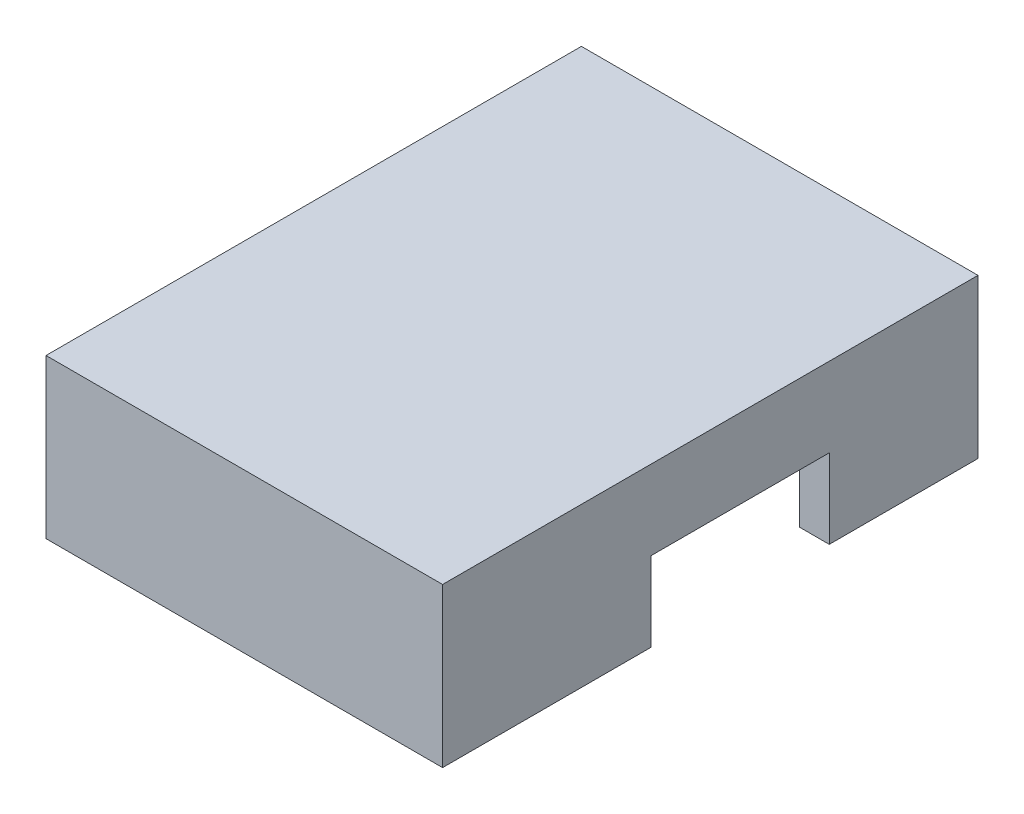
SolidWorks part; units mm, degrees
ref_plane "Front Plane" through (0, 0, 0) normal (0, 0, 1) x (1, 0, 0)
ref_plane "Top Plane" through (0, 0, 0) normal (0, 1, 0) x (1, 0, 0)
ref_plane "Right Plane" through (0, 0, 0) normal (1, 0, 0) x (0, 0, -1)
sketch "Sketch1" plane through (0, 0, 0) normal (0, 1, 0) x (1, 0, 0)
  line L1 (-20.9032, 9.871) -> (-0.9032, 9.871)
  line L2 (-20.9032, 9.871) -> (-20.9032, -17.129)
  line L3 (-20.9032, -17.129) -> (-0.9032, -17.129)
  line L4 (-0.9032, 9.871) -> (-0.9032, -17.129)
  dimension "D1" = 20
  dimension "D2" = 27
extrude "Boss-Extrude1" add sketch "Sketch1" along normal blind 8
sketch "Sketch2" plane through (-20.9032, 0, 0) normal (-1, 0, 0) x (0, 0, 1)
  line L0 (-9.871, 0) -> (17.129, 0) construction
  line L1 (-2.371, 4) -> (6.629, 4)
  line L2 (-2.371, 4) -> (-2.371, 0)
  line L3 (-2.371, 0) -> (6.629, 0)
  line L4 (6.629, 4) -> (6.629, 0)
  line L5 (-9.871, 8) -> (-9.871, 0) construction
  dimension "D1" = 9
  dimension "D2" = 4
  dimension "D3" = 7.5
extrude "Cut-Extrude1" cut sketch "Sketch2" against normal blind 20
sketch "Sketch3" plane through (0, 0, 0) normal (0, -1, 0) x (1, 0, 0)
  line L0 (-0.9032, -2.371) -> (-0.9032, -9.871) construction
  line L1 (-2.4032, -8.371) -> (-19.4032, -8.371)
  line L2 (-2.4032, -8.371) -> (-2.4032, 15.629)
  line L3 (-2.4032, 15.629) -> (-19.4032, 15.629)
  line L4 (-19.4032, -8.371) -> (-19.4032, 15.629)
  line L5 (-20.9032, -9.871) -> (-20.9032, -2.371) construction
  line L6 (-0.9032, -9.871) -> (-20.9032, -9.871) construction
  line L7 (-20.9032, 17.129) -> (-0.9032, 17.129) construction
  dimension "D1" = 1.5
  dimension "D2" = 1.5
  dimension "D3" = 1.5
  dimension "D4" = 1.5
extrude "Cut-Extrude2" cut sketch "Sketch3" against normal blind 5
